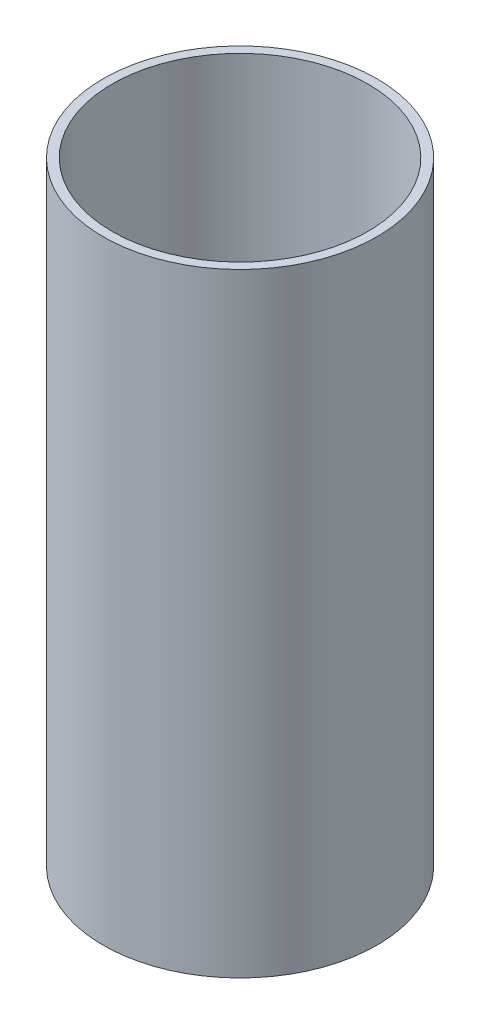
SolidWorks part; units mm, degrees
ref_plane "Front Plane" through (0, 0, 0) normal (0, 0, 1) x (1, 0, 0)
ref_plane "Top Plane" through (0, 0, 0) normal (0, 1, 0) x (1, 0, 0)
ref_plane "Right Plane" through (0, 0, 0) normal (1, 0, 0) x (0, 0, -1)
sketch "Sketch1" plane through (0, 0, 0) normal (0, 0, 1) x (1, 0, 0)
  line L8 (25.4508, 0) -> (27.2542, 0)
  line L9 (25.4508, 0) -> (25.4508, 122.1486)
  line L10 (25.4508, 122.1486) -> (27.2542, 122.1486)
  line L11 (27.2542, 0) -> (27.2542, 122.1486)
  point P5 (24.8925, 11.0975)
  point P6 (0, 0)
  dimension "D1" = 122.1486
  dimension "D2" = 1.8034
  dimension "D3" = 27.2542
ref_axis "Central Axis" through (0, -8.89, 0) along (0, 1, 0)
revolve "Revolve1" add sketch "Sketch1" angle 360 about axis through (0, -8.89, 0) along (0, 1, 0)
